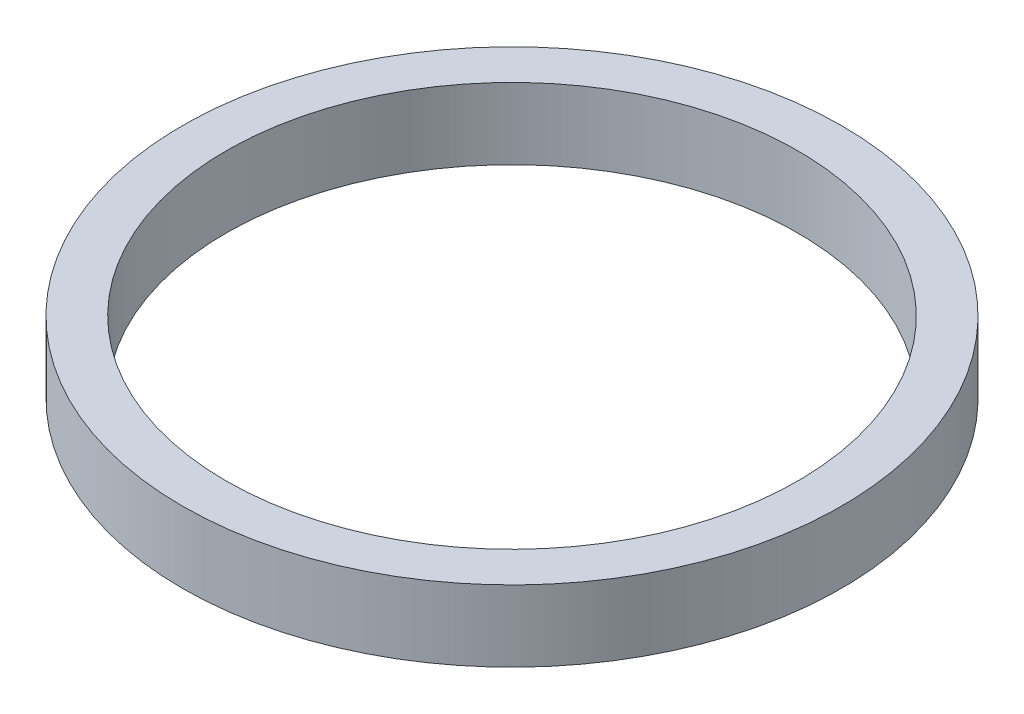
SolidWorks part; units mm, degrees
ref_plane "Front Plane" through (0, 0, 0) normal (0, 0, 1) x (1, 0, 0)
ref_plane "Top Plane" through (0, 0, 0) normal (0, 1, 0) x (1, 0, 0)
ref_plane "Right Plane" through (0, 0, 0) normal (1, 0, 0) x (0, 0, -1)
sketch "Sketch2" plane through (0, 9, 0) normal (0, 1, 0) x (1, 0, 0)
  circle A0 centre (-0.5, 0) radius 18.5 construction
  circle A7 centre (-0.5, 0) radius 18.5
  circle A15 centre (-0.5, 0) radius 16.05
  dimension "D1" = 37
  dimension "D2" = 32.1
extrude "Boss-Extrude1" add sketch "Sketch2" along normal blind 4
